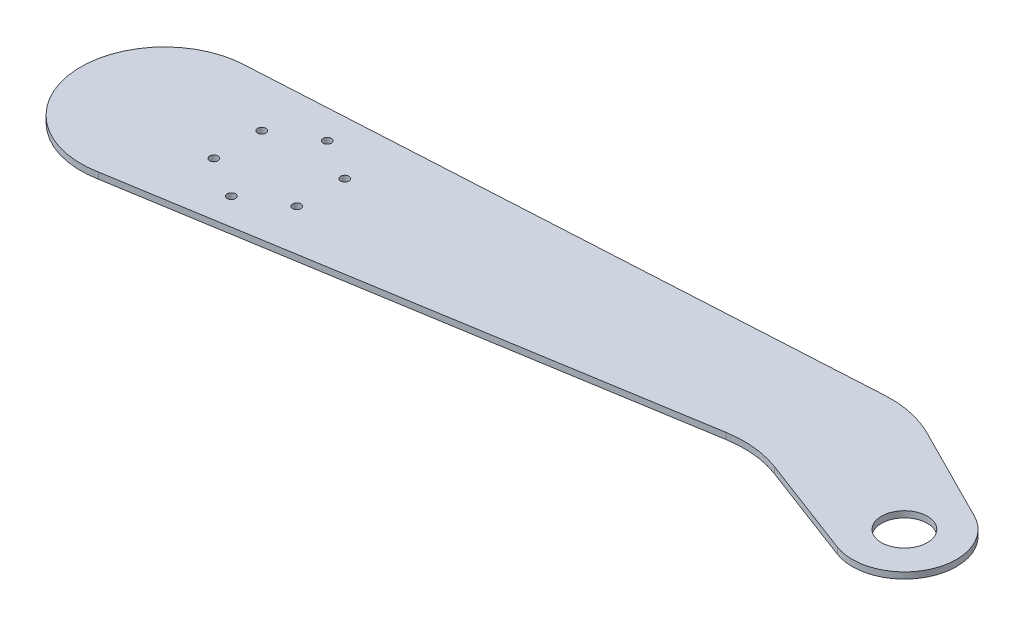
SolidWorks part; units mm, degrees
ref_plane "Front Plane" through (0, 0, 0) normal (0, 0, 1) x (1, 0, 0)
ref_plane "Top Plane" through (0, 0, 0) normal (0, 1, 0) x (1, 0, 0)
ref_plane "Right Plane" through (0, 0, 0) normal (1, 0, 0) x (0, 0, -1)
sketch "Sketch1" plane through (0, 0, 0) normal (0, 1, 0) x (1, 0, 0)
  line L0 (0, 0) -> (300, 0) construction
  line L1 (0, 0) -> (0, 37.5) construction
  line L2 (-2.1002, 37.4411) -> (6.0625, -37.0067) construction
  line L3 (311.2679, 22.3167) -> (291.1646, -23.3867) construction
  line L4 (300, 0) -> (300, 25) construction
  line L5 (-2.1002, 37.4411) -> (701.376, 76.9007)
  line L6 (701.376, 76.9007) -> (6.0625, -37.0067)
  line L7 (291.1646, -23.3867) -> (230.0775, -0.3082)
  line L8 (311.2679, 22.3167) -> (252.9755, 51.7489)
  line L9 (252.9755, 51.7489) -> (230.0775, -0.3082) construction
  line L10 (-2.1002, 37.4411) -> (-50.8208, 34.7083)
  line L11 (-42.0065, -44.8814) -> (6.0625, -37.0067)
  line L12 (-49.702, -5.4508) -> (0, 0) construction
  circle A0 centre (0, 0) radius 37.5
  circle A1 centre (300, 0) radius 11
  circle A2 centre (300, 0) radius 25
  circle A3 centre (0, 0) radius 23 construction
  circle A4 centre (0, 23) radius 2
  circle A5 centre (19.9186, 11.5) radius 2
  circle A6 centre (19.9186, -11.5) radius 2
  circle A7 centre (0, -23) radius 2
  circle A8 centre (-19.9186, -11.5) radius 2
  circle A9 centre (-19.9186, 11.5) radius 2
  arc A10 (-50.8208, 34.7083) -> (-42.0065, -44.8814) centre (-49.702, -5.4508) ccw
  point P11 (325.211, 15.2767)
  point P31 (0, 0)
  dimension "D2" = 75
  dimension "D3" = 22
  dimension "D4" = 50
  dimension "D7" = 46
  dimension "D8" = 4
  dimension "D1" = 300
  dimension "D5" = 150
  dimension "D6" = 150
  dimension "D9" = 6
  dimension "D10" = 50
extrude "Boss-Extrude2" add sketch "Sketch1" along normal blind 3 contours A0 A3 | A2 L8 L5 A0 L6 | A2 L6 L7 | L6 A2 | L6 A2 A1 | L10 A10 L11 A0 region at (-54.9884, 0, 6.0299) region at (145.5999, 0, -15.7285) region at (0, 0, 0) region at (297.2903, 0, -16.5403) region at (261.7379, 0, 4.4957) region at (323.2091, 0, -7.4087)
fillet "Fillet1" radius 50 2 edges at (230.0775, 1.5, 0.3082) (252.9755, 1.5, -51.7489)
sketch "Sketch3" plane through (0, 3, 0) normal (0, 1, 0) x (1, 0, 0)
  line L0 (-49.6973, -5.493) -> (0, 0)
  line L1 (0, 0) -> (496.9735, 54.9302)
  point P1 (394.5655, 43.6111)
  dimension "D1" = 500
